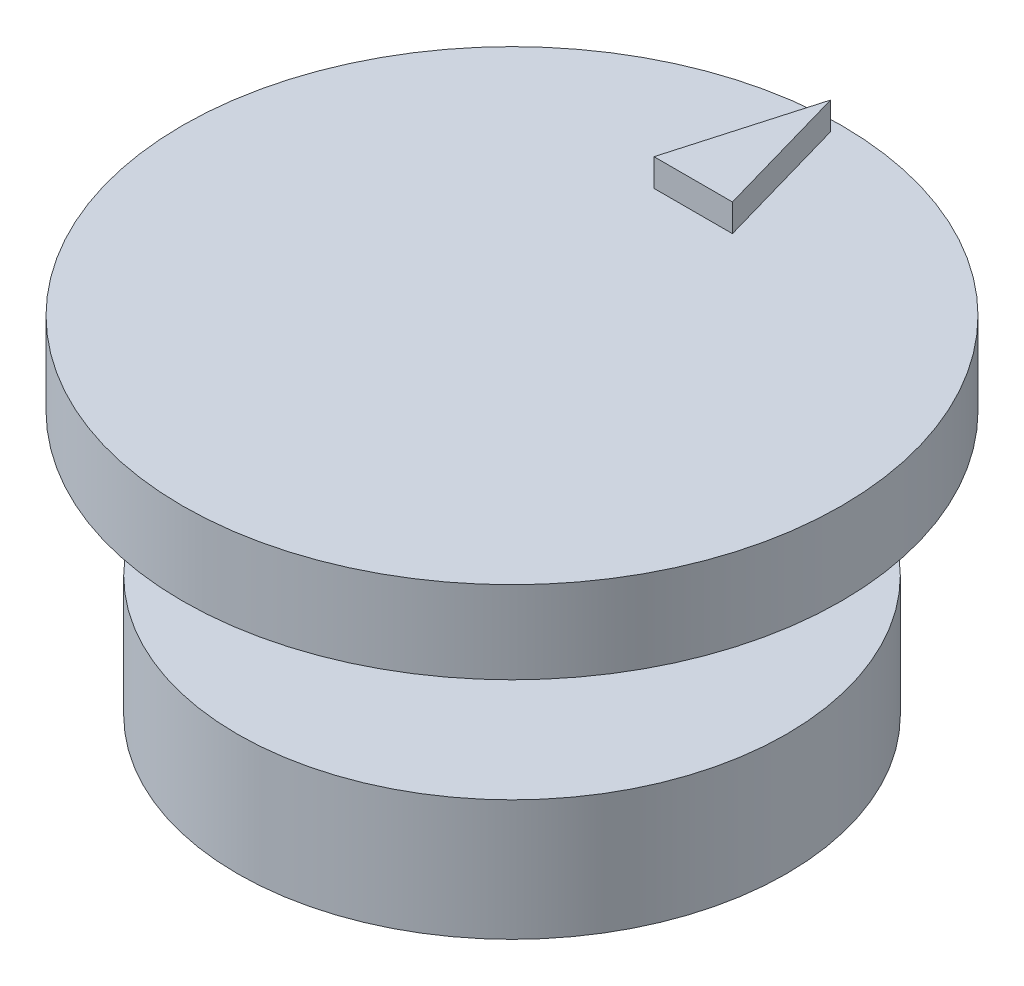
SolidWorks part; units mm, degrees
ref_plane "Front Plane" through (0, 0, 0) normal (0, 0, 1) x (1, 0, 0)
ref_plane "Top Plane" through (0, 0, 0) normal (0, 1, 0) x (1, 0, 0)
ref_plane "Right Plane" through (0, 0, 0) normal (1, 0, 0) x (0, 0, -1)
sketch "Sketch1" plane through (0, 0, 0) normal (0, 0, 1) x (1, 0, 0)
  line L0 (0, -20.8911) -> (0, -36.8931)
  line L1 (0, -36.8931) -> (12.7, -36.8931)
  line L2 (12.7, -36.8931) -> (12.7, -31.3051)
  line L3 (12.7, -31.3051) -> (3.175, -31.3051)
  line L4 (3.175, -31.3051) -> (3.175, -26.2251)
  line L5 (3.175, -26.2251) -> (12.7, -26.2251)
  line L6 (12.7, -26.2251) -> (12.7, -24.7011)
  line L7 (12.7, -24.7011) -> (15.24, -24.7011)
  line L8 (15.24, -24.7011) -> (15.24, -20.8911)
  line L9 (15.24, -20.8911) -> (0, -20.8911)
  dimension "D1" = 3.175
  dimension "D2" = 9.525
  dimension "D3" = 5.08
  dimension "D4" = 5.588
  dimension "D5" = 1.524
  dimension "D6" = 3.81
  dimension "D7" = 12.7
  dimension "D8" = 15.24
revolve "dial base shape" add sketch "Sketch1" angle 360 about L0
sketch "Sketch2" plane through (0, -20.8911, 0) normal (0, 1, 0) x (1, 0, 0)
  line L0 (0, 14.732) -> (-1.8139, 8.382)
  line L1 (-1.8139, 8.382) -> (1.8139, 8.382)
  line L2 (1.8139, 8.382) -> (0, 14.732)
  dimension "D1" = 6.35
  dimension "D2" = 8.382
  dimension "D3" = 6.604
  dimension "D4" = 6.604
extrude "arrow" add sketch "Sketch2" along normal blind 1.27
sketch "Sketch3" plane through (0, -36.8931, 0) normal (0, -1, 0) x (1, 0, 0)
  circle A0 centre (0, -9.8549) radius 1.7989
extrude "flag" add sketch "Sketch3" along normal blind 6.35
